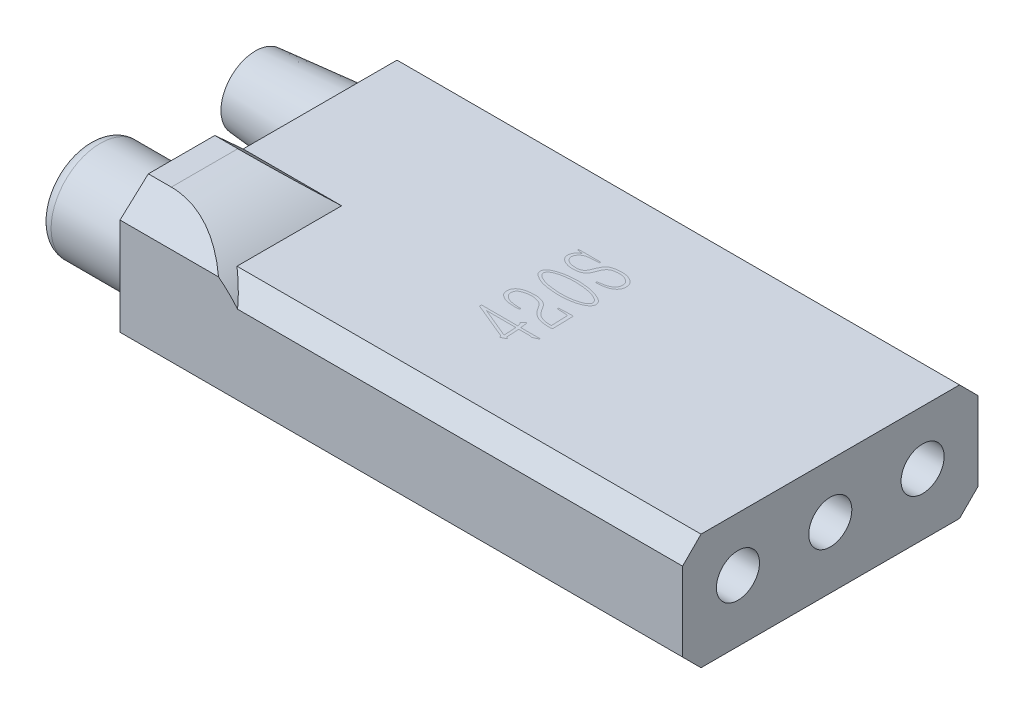
SolidWorks part; units mm, degrees
ref_plane "前视基准面" through (0, 0, 0) normal (0, 0, 1) x (1, 0, 0)
ref_plane "上视基准面" through (0, 0, 0) normal (0, 1, 0) x (1, 0, 0)
ref_plane "右视基准面" through (0, 0, 0) normal (1, 0, 0) x (0, 0, -1)
sketch "草图1" plane through (0, 0, 0) normal (0, 1, 0) x (1, 0, 0)
  line L1 (-22.85, -12) -> (22.85, -12)
  line L2 (-22.85, -12) -> (-22.85, 12)
  line L3 (-22.85, 12) -> (22.85, 12)
  line L4 (22.85, -12) -> (22.85, 12)
  line L5 (-22.85, -12) -> (22.85, 12) construction
  line L6 (-22.85, 12) -> (22.85, -12) construction
  point P0 (0, 0)
  dimension "D1" = 24
  dimension "D2" = 45.7
extrude "凸台-拉伸1" add sketch "草图1" along normal blind 9.4
sketch "草图2" plane through (22.85, 0, 0) normal (1, 0, 0) x (0, 0, -1)
  line L0 (-7.5, 5) -> (7.5, 5) construction
  line L1 (-12, 0) -> (12, 0) construction
  circle A0 centre (-7.5, 5) radius 1.75
  circle A1 centre (0, 5) radius 1.75
  circle A2 centre (7.5, 5) radius 1.75
  dimension "D1" = 3.5
  dimension "D2" = 15
  dimension "D3" = 5
extrude "切除-拉伸1" cut sketch "草图2" against normal blind 6
sketch "草图3" plane through (-22.85, 0, 0) normal (-1, 0, 0) x (0, 0, 1)
  line L0 (-12, 0) -> (12, 0) construction
  line L2 (12, 9.4) -> (12, 0) construction
  circle A0 centre (7, 5) radius 4
  dimension "D1" = 8
  dimension "D3" = 5
  dimension "D2" = 5
extrude "凸台-拉伸2" add sketch "草图3" along normal blind 7.6
sketch "草图4" plane through (-22.85, 0, 0) normal (-1, 0, 0) x (0, 0, 1)
  line L0 (4.3, 11.5) -> (9.7, 11.5)
  line L1 (9.7, 11.5) -> (12, 9.4)
  line L2 (-12, 9.4) -> (12, 9.4) construction
  line L3 (4.3, 11.5) -> (2, 9.4)
  line L4 (2, 9.4) -> (12, 9.4)
  line L5 (-12, 0) -> (12, 0) construction
  line L6 (7, 5) -> (7, 11.5) construction
  line L8 (12, 9.4) -> (12, 0) construction
  point P8 (7, 11.5)
  point P9 (7, 9.4)
  dimension "D1" = 11.5
  dimension "D2" = 5.4
extrude "凸台-拉伸3" add sketch "草图4" against normal blind 8
fillet "圆角1" radius 10 1 edges at (-14.85, 11.5, 7)
chamfer "倒角1" distance 1.5 angle 45 4 edges at (0, 0, -12) (0, 0, 12) (0, 9.4, -12) (4, 9.4, 12)
sketch "草图5" plane through (-22.85, 0, 0) normal (-1, 0, 0) x (0, 0, 1)
  line L0 (-12, 7.9) -> (-12, 1.5) construction
  line L1 (-10.5, 0) -> (10.5, 0) construction
  circle A0 centre (-7, 5) radius 3.5
  dimension "D1" = 7
  dimension "D2" = 5
  dimension "D3" = 5
extrude "凸台-拉伸4" add sketch "草图5" along normal blind 8 draft 5
fillet "圆角2" radius 1 1 edges at (-30.45, 5, 11)
sketch "草图6" plane through (0, 9.4, 0) normal (0, 1, 0) x (1, 0, 0)
  line L0 (2.85, 10.5) -> (2.85, -10.5) construction
  line L1 (22.85, 10.5) -> (-22.85, 10.5) construction
  line L2 (-14.85, -10.5) -> (22.85, -10.5) construction
  line L3 (22.85, -10.5) -> (22.85, 10.5) construction
  text T0 "420S" font "汉仪长仿宋体" height 5
  dimension "D1" = 20
split line "分割线1"
